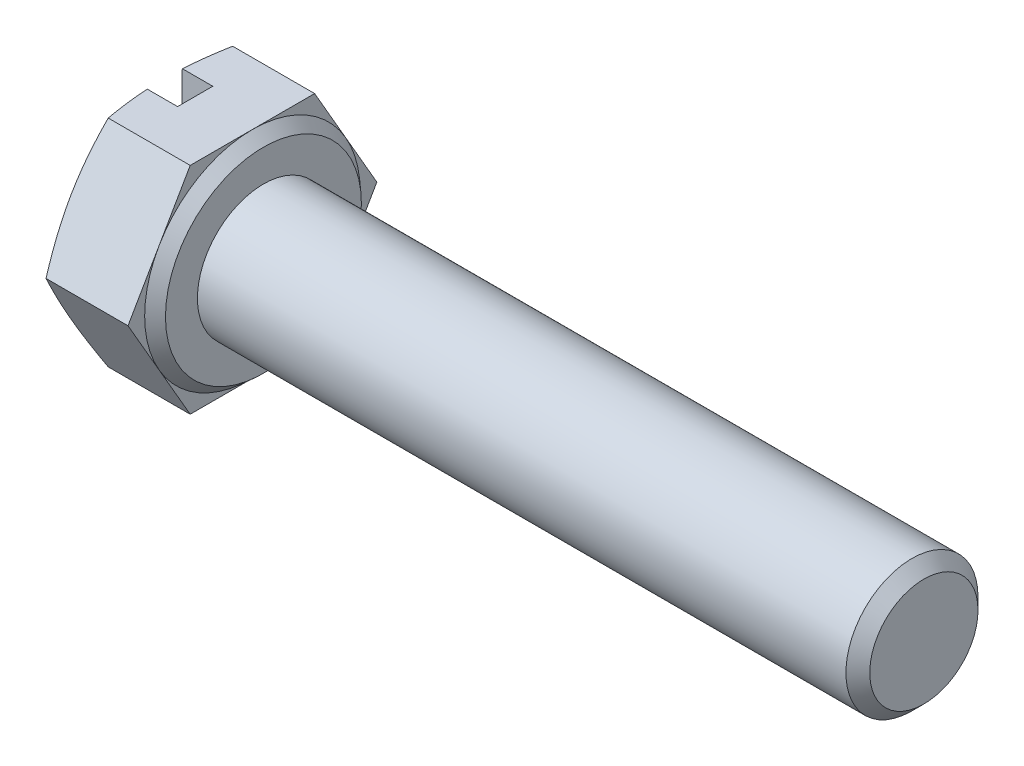
SolidWorks part; units mm, degrees
ref_plane "Front" through (0, 0, 0) normal (0, 0, 1) x (1, 0, 0)
ref_plane "Top" through (0, 0, 0) normal (0, 1, 0) x (1, 0, 0)
ref_plane "Right" through (0, 0, 0) normal (1, 0, 0) x (0, 0, -1)
sketch "Sketch-BaseHead" plane through (0, 0, 0) normal (1, 0, 0) x (0, 0, -1)
  line L1 (2.8261, -4.895) -> (5.6523, 0)
  line L2 (5.6523, 0) -> (2.8261, 4.895)
  line L3 (2.8261, 4.895) -> (-2.8261, 4.895)
  line L4 (-2.8261, 4.895) -> (-5.6523, 0)
  line L5 (-5.6523, 0) -> (-2.8261, -4.895)
  line L6 (-2.8261, -4.895) -> (2.8261, -4.895)
  circle A0 centre (0, 0) radius 4.895 construction
extrude "BaseHead" add sketch "Sketch-BaseHead" along normal blind 4
ref_plane "Plane1" through (4.5, 0, 0) normal (1, 0, 0) x (0, 0, -1)
sketch "Sketch1" plane through (0, 0, 0) normal (0, 0, 1) x (1, 0, 0)
  line L0 (4, 0) -> (4.5, 0)
  line L1 (4.5, 0) -> (4.5, -4.45)
  line L2 (4.5, -4.45) -> (4, -4.895)
  line L3 (4, -4.895) -> (4, 0)
  dimension "D1" = 4.895
  dimension "D3" = 4.45
revolve "Revolve1" add sketch "Sketch1" angle 360 about axis through (-4.0016, 0, 0) along (1, 0, 0)
sketch "Sketch3" plane through (4.5, 0, 0) normal (1, 0, 0) x (0, 0, -1)
  circle A0 centre (0, 0) radius 3
extrude "BaseBody" add sketch "Sketch3" along normal blind 30
cosmetic thread "ThreadCosmetic1" [suppressed] parameters "D2"=4.917
chamfer "Chamfer1" distance 0.5415 angle 45 1 edges at (34.5, 0, -3)
fillet "HeadFillet" [suppressed] radius 0.25
sketch "Sketch4" plane through (-0.2646, 0, 5.9169) normal (0, 1, 0) x (0, 0, -1)
  line L0 (5.9169, 3.7369) -> (5.9169, -10.4477) construction
  line L2 (11.5692, -0.2646) -> (10.8119, -0.2646)
  line L4 (10.8119, -0.2646) -> (11.5692, -0.5403)
  line L6 (11.5692, -0.5403) -> (11.5692, -0.2646)
  dimension "D1" = 20
  dimension "D2" = 9.79
revolve "HeadChamfer" cut sketch "Sketch4" angle 360 about L0
sketch "Sketch5" plane through (0, 0, 0) normal (0, 1, 0) x (1, 0, 0)
  line L0 (0, 0.8) -> (0, -0.8)
  line L1 (1.4, -0.8) -> (1.4, 0.8)
  line L2 (1.4, 0.8) -> (0, 0.8)
  line L3 (0, -0.8) -> (1.4, -0.8)
  dimension "n" = 1.6
  dimension "t" = 1.4
extrude "Slot" cut sketch "Sketch5" against normal through all and the other way through all
sketch "Sketch6" plane through (0, 0, 0) normal (0, 0, 1) x (1, 0, 0)
  line L0 (4.5, 3.2) -> (5.0415, 3.2)
  line L1 (5.0415, 3.2) -> (5.0415, 3)
  line L2 (5.0415, 3) -> (4.7708, 2.531)
  line L3 (4.5, 3) -> (4.7708, 2.531)
  line L4 (4.5, 3.2) -> (4.5, 3)
  line L5 (14.0487, 0) -> (0, 0) construction
  line L6 (4.5, 3) -> (5.0415, 3) construction
  line L7 (4.7708, 3) -> (4.7708, 2.531) construction
  point P5 (4.7708, 3.2)
  dimension "D2" = 0.5415
revolve "Cut-Revolve10" [suppressed] cut sketch "Sketch6" angle 360 about L5
pattern_linear "LPattern10" [suppressed] count 46 spacing 0.6498 of bodies 108
equation "\"D1@Sketch1\" = \"s@Sketch-BaseHead\"/ 2 "
equation "\"D2@Sketch4\" = \"s@Sketch-BaseHead\""
equation "\"D1@Chamfer1\" =  ( \"d@Sketch3\" - \"D2@ThreadCosmetic1\" ) / 2 "
equation "\"D2@Sketch6\" = (  \"d@Sketch3\" - \"D2@ThreadCosmetic1\" )  / 2"
equation "\"D3@LPattern10\" = \"D2@Sketch6\" * 1.2"
equation "\"D1@LPattern10\" = \"l@BaseBody\" / \"D3@LPattern10\""
